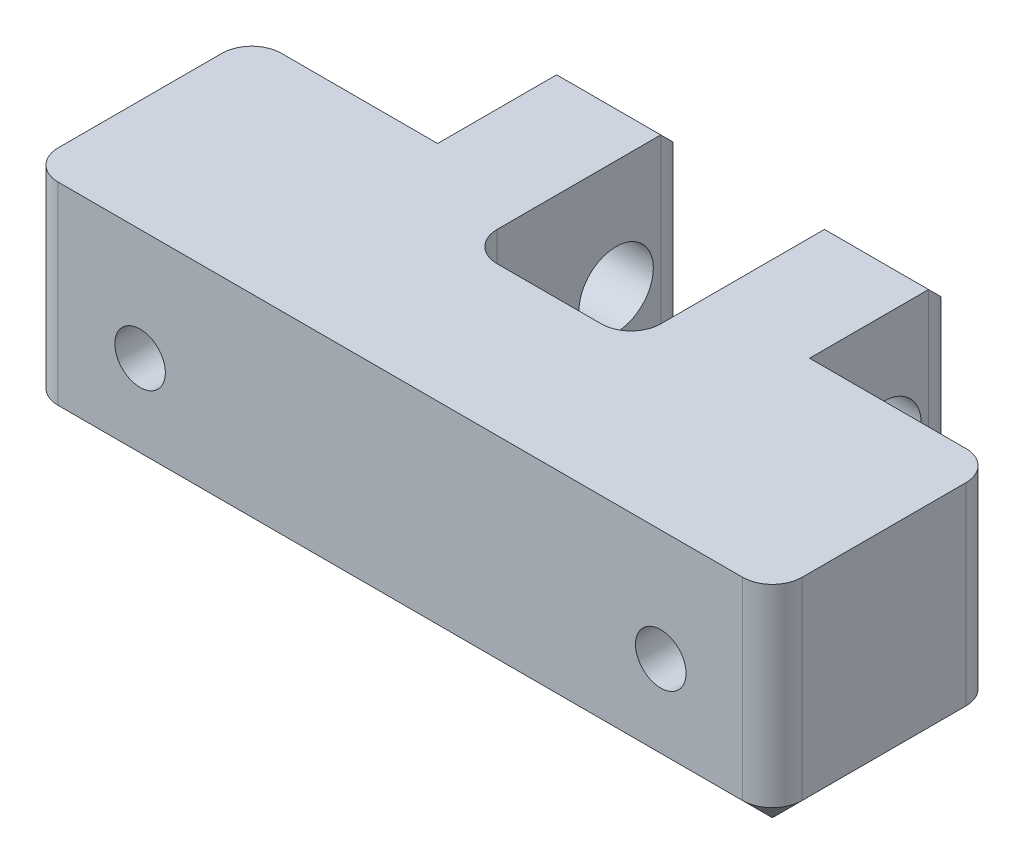
SolidWorks part; units mm, degrees
ref_plane "Front Plane" through (0, 0, 0) normal (0, 0, 1) x (1, 0, 0)
ref_plane "Top Plane" through (0, 0, 0) normal (0, 1, 0) x (1, 0, 0)
ref_plane "Right Plane" through (0, 0, 0) normal (1, 0, 0) x (0, 0, -1)
ref_plane "Top of part" through (0, 15, 0) normal (0, 1, 0) x (1, 0, 0)
sketch "Main Body Sketch" plane through (0, 0, 0) normal (0, 1, 0) x (1, 0, 0)
  line L0 (-12.5, 20) -> (-12.5, 10)
  line L6 (-25, 0) -> (-25, -5)
  line L7 (-25, 0) -> (-25, 10)
  line L8 (-5.5, 20) -> (-5.5, 5)
  line L9 (-12.5, 20) -> (-5.5, 20)
  line L10 (5.5, 5) -> (5.5, 20)
  line L11 (5.5, 20) -> (12.5, 20)
  line L12 (12.5, 10) -> (12.5, 20)
  line L13 (-5.5, 5) -> (5.5, 5)
  line L15 (-25, -5) -> (25, -5)
  line L17 (-25, 10) -> (-12.5, 10)
  line L19 (12.5, 10) -> (25, 10)
  line L20 (25, 10) -> (25, -5)
  point P0 (0, 0)
  point P6 (0, 0)
  point P12 (0, 0)
  point P14 (25, 1.6592)
  point P19 (25, -9.645)
  dimension "D1" = 50
  dimension "D2" = 7
  dimension "D3" = 11
  dimension "D4" = 25
  dimension "D5" = 5
  dimension "D6" = 5
  dimension "D7" = 10
  dimension "D8" = 15
extrude "Main Block" add sketch "Main Body Sketch" along normal up to surface (15 mm away) up to plane "Top of part"
sketch "Tension Bolt Holes Position Sketch" plane through (0, 0, -10) normal (0, 0, -1) x (-1, 0, 0)
  line L0 (-17.5, 0) -> (17.5, 0) construction
  point P0 (-17.5, 7.5)
  point P1 (17.5, 7.5)
  point P2 (0, 0)
  point P3 (0, 0)
  point P4 (-17.5, 8.0814)
  point P6 (0, 0)
  point P8 (0, 0)
  point P9 (0, 0)
  dimension "D1" = 35
  dimension "D2" = 7.5
hole_wizard "Tension Screw Holes" positions "Sketch3" profile "Sketch4" counterbore size "M3" standard "ISO" end condition through all
sketch "Sketch3" plane through (0, 0, -10) normal (0, 0, -1) x (-1, 0, 0)
  point P0 (17.5, 7.5)
  point P3 (-17.5, 7.5)
sketch "Sketch4" plane through (-17.5, 7.5, -10) normal (1, 0, 0) x (0, 1, 0)
  line L0 (0, 0) -> (0, 15)
  line L1 (0, 15) -> (1.7, 15)
  line L3 (1.7, 15) -> (1.7, 3.4)
  line L4 (1.7, 3.4) -> (3.25, 3.4)
  line L5 (3.25, 3.4) -> (3.25, 0)
  line L7 (3.25, 0) -> (0, 0)
  line L11 (0, -6.35) -> (0, 107.95) construction
  dimension "Thru Hole Dia." = 3.4
  dimension "Thru Hole Depth" = 15
  dimension "C'Bore Dia." = 6.5
  dimension "C'Bore Depth" = 3.4
sketch "Idler Mounting Bolt Position" plane through (12.5, 0, 0) normal (1, 0, 0) x (0, 0, -1)
  point P0 (15, 7.5)
  dimension "D1" = 5
  dimension "D2" = 7.5
hole_wizard "Idler Mounting Hole" positions "Sketch6" profile "Sketch8" hole size "Ø5.0" standard "ISO" end condition through all
sketch "Sketch6" plane through (12.5, 0, 0) normal (1, 0, 0) x (0, 0, -1)
  point P0 (15, 7.5)
sketch "Sketch8" plane through (12.5, 7.5, -15) normal (0, 1, 0) x (0, 0, -1)
  line L0 (0, 0) -> (0, 37.5)
  line L1 (0, 37.5) -> (2.5, 37.5)
  line L2 (2.5, 37.5) -> (2.5, 0)
  line L5 (2.5, 0) -> (0, 0)
  line L11 (0, -6.35) -> (0, 107.95) construction
  dimension "Thru Hole Dia." = 5
  dimension "Thru Hole Depth" = 37.5
chamfer "Cosmetic Chamfer" distance 2 angle 45 4 edges at (9, 15, -20) (-9, 15, -20) (-9, 0, -20) (9, 0, -20)
fillet "Print Helper Fillets" radius 2 10 edges at (-5.5, 7.5, -5) (5.5, 7.5, -5) (-12.5, 7.5, -20) (-5.5, 7.5, -20) (5.5, 7.5, -20) (12.5, 7.5, -20) (-25, 7.5, 5) (25, 7.5, -10) (25, 7.5, 5) (-25, 7.5, -10)
chamfer "Cosmetic Chamfers" distance 2 angle 45 11 edges at (-17.75, 0, -10) (-24.4142, 0, -9.4142) (-25, 0, -2.5) (-24.4142, 0, 4.4142) (0, 0, 5) (17.75, 0, -10) (24.4142, 0, 4.4142) (24.4142, 0, -9.4142) (25, 0, -2.5) (-12.5, 0, -14) (12.5, 0, -14)
